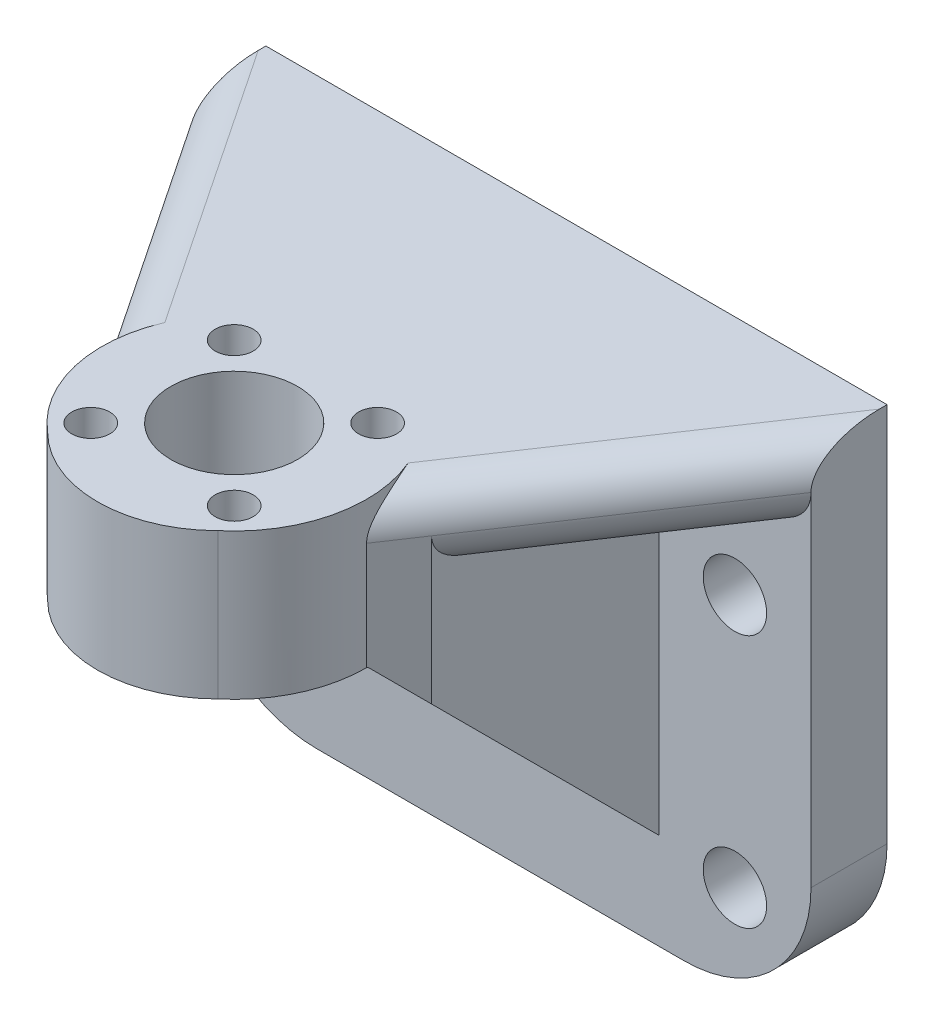
SolidWorks part; units mm, degrees
ref_plane "前基準面" through (0, 0, 0) normal (0, 0, 1) x (1, 0, 0)
ref_plane "上基準面" through (0, 0, 0) normal (0, 1, 0) x (1, 0, 0)
ref_plane "右基準面" through (0, 0, 0) normal (1, 0, 0) x (0, 0, -1)
sketch "草圖1" plane through (0, 0, 0) normal (0, 1, 0) x (1, 0, 0)
  line L0 (0, -9.5) -> (27.6564, -9.5) construction
  line L1 (24.5, -17.5) -> (-24.5, -17.5)
  line L2 (24.5, -17.5) -> (24.5, 17.5)
  line L3 (24.5, 17.5) -> (-24.5, 17.5)
  line L4 (-24.5, -17.5) -> (-24.5, 17.5)
  line L5 (0, 17.5) -> (0, -17.5) construction
  line L6 (24.5, 0) -> (-24.5, 0) construction
  line L7 (-24.5, 11.5) -> (24.5, 11.5)
  line L8 (0, -9.5) -> (5.6569, -3.8431)
  circle A0 centre (0, -9.5) radius 4
  circle A2 centre (5.6569, -3.8431) radius 1.5
  circle A6 centre (5.6569, -15.1569) radius 1.5
  circle A7 centre (-5.6569, -15.1569) radius 1.5
  circle A8 centre (-5.6569, -3.8431) radius 1.5
  point P0 (0, 0)
  dimension "D3" = 8
  dimension "D4" = 3
  dimension "D1" = 35
  dimension "D2" = 49
  dimension "D5" = 6
  dimension "D6" = 21
  dimension "D7" = 8
extrude "填料-伸長1" add sketch "草圖1" along normal blind 40 contours L3 L4 L1 L2
sketch "草圖2" plane through (0, 40, 0) normal (0, 1, 0) x (1, 0, 0)
  line L0 (0, -9.5) -> (5.6569, -3.8431)
  line L1 (0, -9.5) -> (24.2352, -9.5)
  line L2 (-24.5, 11.5) -> (24.5, 11.5)
  line L3 (-24.5, -17.5) -> (-24.5, 17.5) construction
  line L4 (24.5, -17.5) -> (24.5, 17.5) construction
  line L5 (24.5, 17.5) -> (-24.5, 17.5) construction
  line L6 (0, -9.5) -> (0, 11.5) construction
  circle A0 centre (0, -9.5) radius 5
  circle A1 centre (5.6569, -3.8431) radius 1.5
  circle A2 centre (5.6569, -15.1569) radius 1.5
  circle A3 centre (-5.6569, -15.1569) radius 1.5
  circle A4 centre (-5.6569, -3.8431) radius 1.5
  dimension "D1" = 3
  dimension "D2" = 10
  dimension "D3" = 8
  dimension "D4" = 45
  dimension "D5" = 6
  dimension "D6" = 21
extrude "除料-伸長1" cut sketch "草圖2" against normal blind 40
sketch "草圖3" plane through (0, 0, 17.5) normal (0, 0, 1) x (1, 0, 0)
  line L0 (0, 40) -> (0, 0)
  line L1 (24.5, 40) -> (-24.5, 40) construction
  line L2 (-24.5, 20) -> (24.5, 20)
  line L3 (-24.5, 40) -> (-24.5, 0) construction
  line L4 (24.5, 40) -> (24.5, 0) construction
  line L5 (24.5, 0) -> (12.5, 0)
  line L6 (12.5, 0) -> (-12.5, 0)
  line L7 (12.5, 0) -> (12.5, 40)
  line L8 (12.5, 40) -> (-12.5, 40)
  line L9 (-12.5, 0) -> (-12.5, 40)
  line L10 (0, 40) -> (0, 0) construction
  line L11 (12.5, 20) -> (-12.5, 20) construction
  line L20 (-24.5, 34) -> (-12.5, 34)
  line L21 (-24.5, 34) -> (-24.5, 0)
  line L22 (-24.5, 0) -> (-12.5, 0)
  line L23 (-12.5, 34) -> (-12.5, 0)
  line L24 (12.5, 34) -> (12.5, 0)
  line L25 (24.5, 34) -> (12.5, 34)
  line L26 (24.5, 34) -> (24.5, 0)
  point P11 (0, 20)
  line M13 (-24.5, 0) -> (24.5, 0)
  line M14 (24.5, 0) -> (24.5, 40)
  line M15 (24.5, 40) -> (-24.5, 40)
  line M16 (-24.5, 40) -> (-24.5, 0)
  dimension "D1" = 25
  dimension "D2" = 6
extrude "除料-伸長3" cut sketch "草圖3" against normal blind 29 contours L2 L9 M15 M16 | L9 L2 M13 M16 | L7 L2 M13 M14 | L7 L2 M14 M15
sketch "草圖6" plane through (0, 40, 0) normal (0, 1, 0) x (1, 0, 0)
  line L0 (-24.5, 11.5) -> (-9.9617, 11.5)
  line L1 (-24.5, -17.5) -> (-24.5, 17.5) construction
  line L2 (24.5, 17.5) -> (-24.5, 17.5) construction
  line L3 (-24.5, 11.5) -> (-10.4449, -9.5)
  line L4 (10.4449, -9.5) -> (24.5, 11.5)
  circle A0 centre (0, -9.5) radius 10.4449
  line M6 (24.5, -17.5) -> (24.5, 17.5)
  line M8 (-24.5, 17.5) -> (-24.5, -17.5)
  line M9 (-24.5, -17.5) -> (24.5, -17.5)
  dimension "D1" = 6
extrude "除料-伸長6" cut sketch "草圖6" against normal blind 50 contours A0 L3 M8 M9 | A0 L4 M9 M6
sketch "草圖7" plane through (0, 0, 17.5) normal (0, 0, 1) x (1, 0, 0)
  line L0 (6.7154, 40) -> (-6.7154, 40) construction
  line L1 (-10.5, 28.5) -> (10.5, 28.5)
  line L2 (-10.5, 28.5) -> (-10.5, 0)
  line L3 (-10.5, 0) -> (10.5, 0)
  line L4 (0, 28.5) -> (0, 0)
  line L5 (-12.5, 0) -> (-12.5, 34) construction
  line L6 (10.5, 28.5) -> (10.5, 0)
  dimension "D1" = 11.5
  dimension "D2" = 2
extrude "除料-伸長8" cut sketch "草圖7" against normal blind 29 contours L2 L3 L6 L1
sketch "草圖10" plane through (-12.5, 0, 0) normal (-1, 0, 0) x (0, 0, 1)
  line L0 (9.4177, 28.5) -> (-11.5, 28.5) construction
  line L6 (-11.5, 0) -> (6.4294, 0)
  line L8 (-11.5, 34) -> (-11.5, 0) construction
  line L9 (9.4177, 28.5) -> (-3.3195, 15.7628) construction
  line L10 (9.4177, 28.5) -> (-11.5, 7.5823)
  line L11 (-11.5, 0) -> (-11.5, 34) construction
  line L12 (-11.5, 7.5823) -> (-11.5, 0)
  line L13 (6.4294, 0) -> (9.4177, 0)
  line L14 (9.4177, 0) -> (9.4177, 28.5)
  dimension "D1" = 45
extrude "除料-伸長10" cut sketch "草圖10" against normal blind 29 contours L6 L13 L14 L10 L12
sketch "草圖12" plane through (0, 0, -11.5) normal (0, 0, 1) x (1, 0, 0)
  line L0 (-12.5, 21.456) -> (-24.5, 21.456) construction
  line L1 (-12.5, 7.5823) -> (-12.5, 34) construction
  line L2 (-24.5, 34) -> (-24.5, 0) construction
  line L5 (-12.5, 34) -> (-24.5, 34) construction
  line L6 (0, 40) -> (0, -1.2968) construction
  line L7 (6.7154, 40) -> (-6.7154, 40) construction
  circle A0 centre (-18.5, 27) radius 2.5
  circle A1 centre (-18.5, 7) radius 2.5
  circle A2 centre (18.5, 7) radius 2.5
  circle A3 centre (18.5, 27) radius 2.5
  dimension "D1" = 5
  dimension "D3" = 5
  dimension "D2" = 7
  dimension "D4" = 20
extrude "除料-伸長12" cut sketch "草圖12" against normal through all contours A2 | A3 | A1 | A0
fillet "圓角1" radius 10 1 edges at (-24.5, 0, -14.5)
fillet "圓角2" radius 10 1 edges at (24.5, 0, -14.5)
fillet "圓角4" radius 3 4 edges at (18.5, 34, -2.5353) (17.4725, 40, -1) (-17.4725, 40, -1) (-18.5, 34, -2.5353)
sketch "草圖14" plane through (0, 40, 0) normal (0, 1, 0) x (1, 0, 0)
  line L6 (9.5958, -5.375) -> (24.5, 16.8937)
  line L7 (24.5, 16.8937) -> (24.5, 17.5)
  line L8 (24.5, 17.5) -> (-24.5, 17.5)
  line L9 (-24.5, 17.5) -> (-24.5, 16.8937)
  line L10 (-24.5, 16.8937) -> (-9.5958, -5.375)
  line L11 (-6.7154, -17.5) -> (6.7154, -17.5)
  line L17 (-6.7154, -17.5) -> (6.7154, -17.5)
  arc A0 (-6.7154, -17.5) -> (6.7154, -17.5) centre (0, -10.7846) ccw
  arc A3 (6.7154, -17.5) -> (9.5958, -5.375) centre (0, -9.5) ccw
  arc A4 (-9.5958, -5.375) -> (-6.7154, -17.5) centre (0, -9.5) ccw
  dimension "D1" = 0
extrude "填料-伸長2" add sketch "草圖14" against normal blind 11.5
